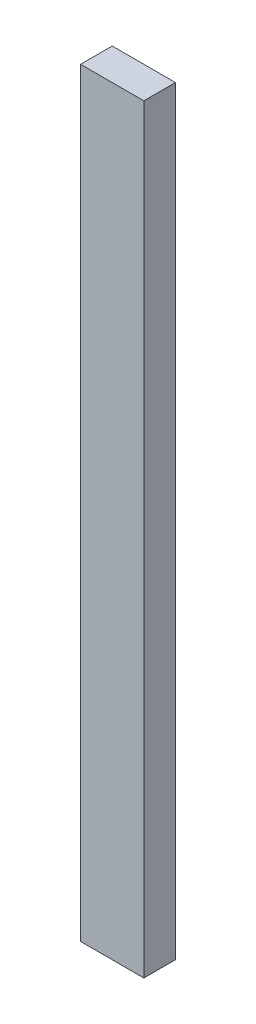
SolidWorks part; units mm, degrees
ref_plane "Front Plane" through (0, 0, 0) normal (0, 0, 1) x (1, 0, 0)
ref_plane "Top Plane" through (0, 0, 0) normal (0, 1, 0) x (1, 0, 0)
ref_plane "Right Plane" through (0, 0, 0) normal (1, 0, 0) x (0, 0, -1)
sketch "Sketch1" plane through (0, 0, 0) normal (0, 0, 1) x (1, 0, 0)
  line L1 (0, 0) -> (6.35, 0)
  line L2 (0, 0) -> (0, 76.2)
  line L3 (0, 76.2) -> (6.35, 76.2)
  line L4 (6.35, 0) -> (6.35, 76.2)
  dimension "D1" = 76.2
  dimension "D2" = 6.35
extrude "Boss-Extrude1" add sketch "Sketch1" along normal blind 3.175
extrude "Boss-Extrude2" add sketch "Sketch1<3>" along normal blind 3.175
sketch "Sketch1<3>" plane through (0, 0, 0) normal (0, 0, 1) x (1, 0, 0) same geometry as "Sketch1"
